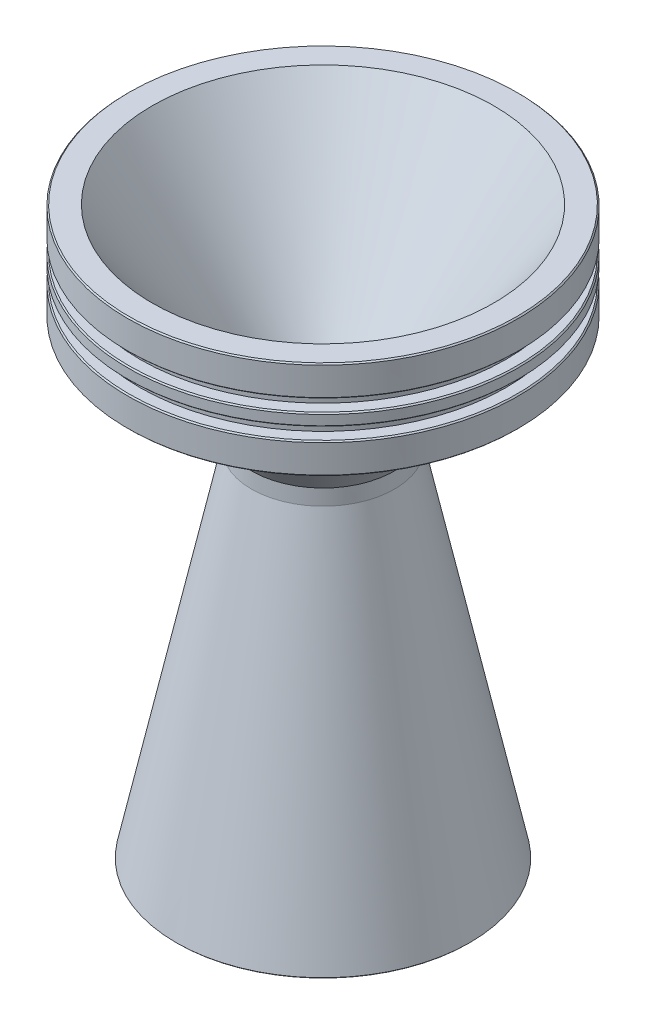
SolidWorks part; units mm, degrees
ref_plane "Front Plane" through (0, 0, 0) normal (0, 0, 1) x (1, 0, 0)
ref_plane "Top Plane" through (0, 0, 0) normal (0, 1, 0) x (1, 0, 0)
ref_plane "Right Plane" through (0, 0, 0) normal (1, 0, 0) x (0, 0, -1)
sketch "Sketch1" plane through (0, 0, 0) normal (0, 0, 1) x (1, 0, 0)
  line L0 (0, 0) -> (2.54, 0)
  line L8 (0, 0) -> (0, -3.175)
  line L9 (0, -3.175) -> (1.27, -3.175)
  line L10 (1.27, -3.175) -> (1.27, -4.445)
  line L11 (1.27, -4.445) -> (0, -4.445)
  line L12 (0, -4.445) -> (0, -5.715)
  line L13 (0, -5.715) -> (1.27, -5.715)
  line L14 (1.27, -5.715) -> (1.27, -6.985)
  line L15 (1.27, -6.985) -> (0, -6.985)
  line L16 (0, -6.985) -> (0, -10.16)
  line L18 (0, 0) -> (20.32, 0) construction
  line L19 (20.32, 0) -> (20.32, -58.9914) construction
  line L20 (2.54, 0) -> (16.129, -19.4071)
  line L22 (8.255, -58.9914) -> (5.0091, -58.9914)
  line L24 (16.129, -19.4071) -> (16.129, -21.9471)
  line L25 (16.129, -21.9471) -> (8.255, -58.9914)
  line L27 (20.32, -58.9914) -> (8.255, -58.9914) construction
  line L29 (5.7781, -10.16) -> (0, -10.16)
  line L30 (12.8831, -21.9471) -> (16.129, -21.9471) construction
  line L33 (12.8831, -20.3069) -> (5.7781, -10.16)
  line L34 (12.8831, -21.9471) -> (5.0091, -58.9914)
  line L35 (12.8831, -20.3069) -> (12.8831, -21.9471)
  line L36 (12.8831, -20.3069) -> (16.129, -19.4071) construction
  dimension "D1" = 2.54
  dimension "D2" = 1.27
  dimension "D3" = 1.27
  dimension "D4" = 3.175
  dimension "D5" = 1.27
  dimension "D6" = 20.32
  dimension "D7" = 2.54
  dimension "D8" = 35
  dimension "D9" = 12
  dimension "D10" = 3.175
  dimension "D11" = 4.191
  dimension "D12" = 3.175
  dimension "D13" = 3.175
  dimension "D14" = 12.065
  dimension "D15" = 15.3109
  dimension "D16" = 37.0443
  dimension "D17" = 58.9914
revolve "base_revolve" add sketch "Sketch1" angle 360 about L19
chamfer "outer_chamfers" distance 0.127 angle 45 7 edges at (0, -10.16, 0) (0, 0, 0) (5.0091, -58.9914, 0) (0, -5.715, 0) (0, -6.985, 0) (0, -4.445, 0) (0, -3.175, 0) first distance on face at (5.7781, -10.16, 0) first distance on face at (0, -3.175, 0) first distance on face at (8.255, -58.9914, 0) first distance on face at (1.27, -5.715, 0) first distance on face at (0, -6.985, 0) first distance on face at (0, -5.715, 0) first distance on face at (1.27, -3.175, 0)
